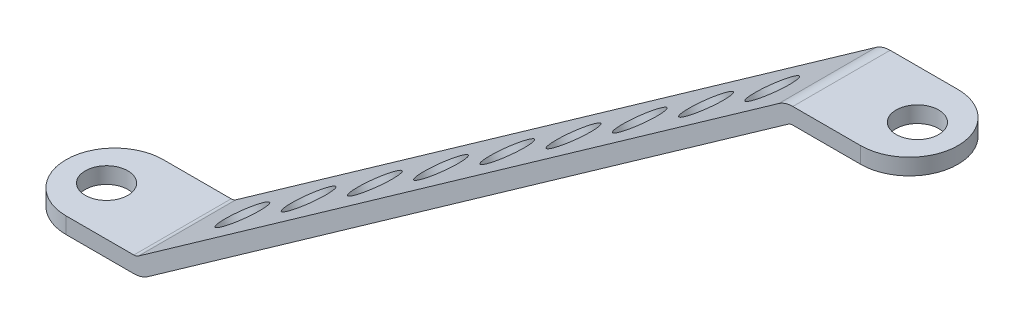
SolidWorks part; units mm, degrees
material "1060 Alloy"
ref_plane "Front Plane" through (0, 0, 0) normal (0, 0, 1) x (1, 0, 0)
ref_plane "Top Plane" through (0, 0, 0) normal (0, 1, 0) x (1, 0, 0)
ref_plane "Right Plane" through (0, 0, 0) normal (1, 0, 0) x (0, 0, -1)
sketch "Sketch1" plane through (0, 0, 0) normal (0, 0, 1) x (1, 0, 0)
  line L0 (0, 0) -> (11.492, 0)
  line L1 (12.415, 0.2931) -> (75.585, 44.9069)
  line L2 (76.508, 45.2) -> (88, 45.2)
  arc A0 (75.585, 44.9069) -> (76.508, 45.2) centre (76.508, 43.6) cw
  arc A1 (11.492, 0) -> (12.415, 0.2931) centre (11.492, 1.6) ccw
  point P7 (76, 45.2)
  point P10 (12, 0)
  dimension "D5" = 1.6
  dimension "D1" = 12
  dimension "D2" = 12
  dimension "D3" = 45.2
  dimension "D4" = 88
extrude "Extrude-Thin1" add sketch "Sketch1" along normal blind 4.8 thin thin type mid plane wall 1.6
sketch "Sketch2" plane through (0, 0.8, 0) normal (0, 1, 0) x (1, 0, 0)
  line L0 (0, 0) -> (11.492, 0) construction
  circle A0 centre (4, 0) radius 2.1
  dimension "D1" = 4.2
  dimension "D2" = 4
extrude "Cut-Extrude1" cut sketch "Sketch2" against normal through all
sketch "Sketch3" plane through (0, 46, 0) normal (0, 1, 0) x (1, 0, 0)
  line L0 (76.508, 0) -> (88, 0) construction
  circle A0 centre (84, 0) radius 2.1
  dimension "D2" = 4.2
  dimension "D1" = 4
extrude "Cut-Extrude2" cut sketch "Sketch3" against normal through all
fillet "Fillet1" radius 4.8 2 edges at (0, 0, 4.8) (88, 45.2, 4.8)
sketch "Sketch4" plane through (3.532, -5.0011, 0) normal (-0.5769, 0.8168, 0) x (0.8168, 0.5769, 0)
  line L0 (48.9779, -16.9131) -> (48.9779, 16.014) construction
  line L1 (96.8654, 0) -> (98.4174, 0) construction
  line L2 (-0.4615, 0) -> (1.0905, 0) construction
  line L3 (96.8654, 0) -> (98.4174, 0) construction
  line L4 (-0.4615, 0) -> (1.0905, 0) construction
  line L5 (10.31, 0) -> (87.6459, 0) construction
  circle A0 centre (48.9779, 0) radius 2.1
  dimension "D1" = 4.2
extrude "Cut-Extrude3" cut sketch "Sketch4" against normal through all
pattern_linear "LPattern1" count 5 spacing 8 along (0.8168, 0.5769, 0) of "Cut-Extrude3"
pattern_linear "LPattern2" count 5 spacing 8 along (-0.8168, -0.5769, 0) of "Cut-Extrude3"
mirror "Mirror1" about plane through (76.508, 43.6, 0) normal (0, 0, 1) of bodies 106
